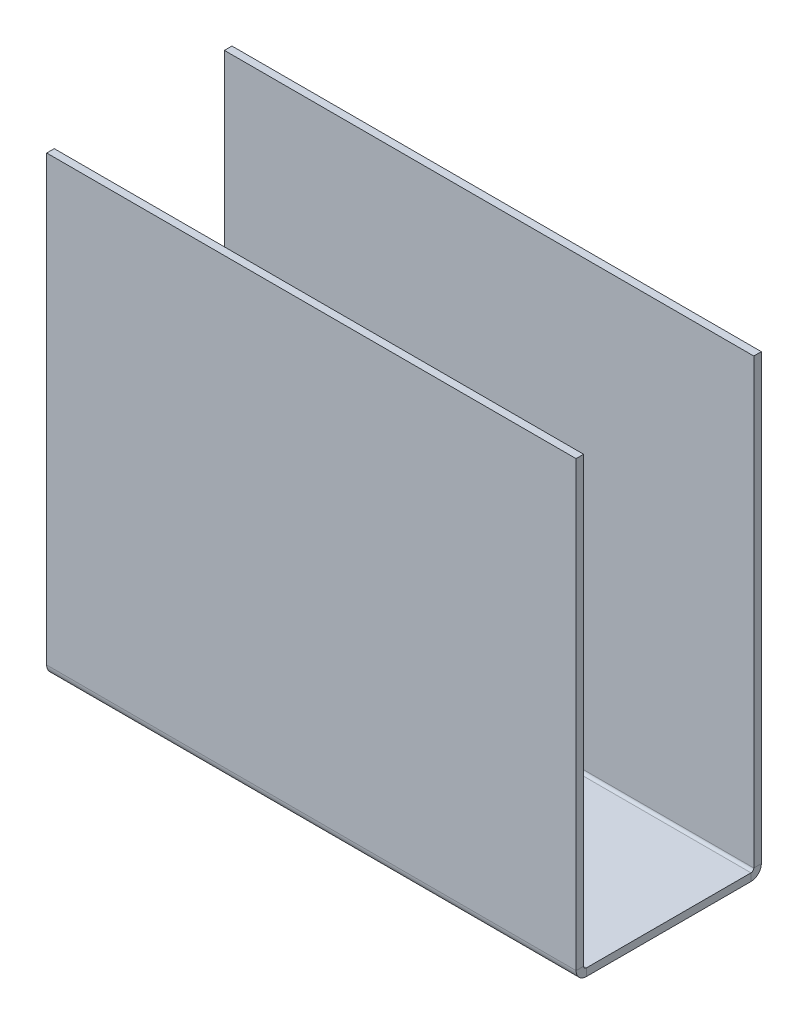
SolidWorks part; units mm, degrees
note: The reader was unsure of these and kept them because the rebuilt part matched: flange length of "Edge-Flange1".
ref_plane "Front Plane" through (0, 0, 0) normal (0, 0, 1) x (1, 0, 0)
ref_plane "Top Plane" through (0, 0, 0) normal (0, 1, 0) x (1, 0, 0)
ref_plane "Right Plane" through (0, 0, 0) normal (1, 0, 0) x (0, 0, -1)
sketch "Sketch1" plane through (0, 0, 0) normal (0, 1, 0) x (1, 0, 0)
  line L1 (-113.3849, 12.7788) -> (26.6151, 12.7788)
  line L2 (-113.3849, 12.7788) -> (-113.3849, -36.2212)
  line L3 (-113.3849, -36.2212) -> (26.6151, -36.2212)
  line L4 (26.6151, 12.7788) -> (26.6151, -36.2212)
  dimension "D1" = 140
  dimension "D2" = 49
base flange "Base-Flange1" sketch "Sketch1" thickness 2 reverse thickness direction no parameters "D1"=0.7366
edge flange "Edge-Flange1" sketch "Sketch8" flange profiles "Sketch8", "Sketch10" flange angle 90 flange length 120 flange position material inside bend radius 0.7366 thickness 2 relief rectangular parameters "D6"=10, "D8"=1
sketch "Sketch8" plane through (0, 0, -12.7788) normal (0, 0, -1) x (-1, 0, 0)
  line L0 (-26.6151, 0) -> (113.3849, 0) construction
  line L1 (-26.6151, 0) -> (113.3849, 0)
  line L2 (-26.6151, 0) -> (-26.6151, 118)
  line L3 (-26.6151, 118) -> (113.3849, 118)
  line L4 (113.3849, 118) -> (113.3849, 0)
sketch "Sketch10" plane through (0, 0, 36.2212) normal (0, 0, 1) x (1, 0, 0)
  line L0 (-113.3849, 0) -> (26.6151, 0) construction
  line L1 (-113.3849, 0) -> (26.6151, 0)
  line L2 (-113.3849, 0) -> (-113.3849, 118)
  line L3 (-113.3849, 118) -> (26.6151, 118)
  line L4 (26.6151, 118) -> (26.6151, 0)
bend "EdgeBend1" bend radius 0.7366 bend angle 90 parameters "D5"=1
bend "EdgeBend2" bend radius 0.7366 bend angle 90 parameters "D5"=3
sketch "Bend-Lines1" [suppressed] plane through (0, 0, 0) normal (0, 1, 0) x (1, 0, 0)
sketch "Bounding-Box1" [suppressed] plane through (0, 0, 0) normal (0, 1, 0) x (1, 0, 0)
sheet metal parameters "Sheet-Metal1" thickness 2 parameters "D1"=0.7366
flat pattern "Flat-Pattern1" [suppressed]
sketch "Bend-Lines2" plane through (0, 0, 0) normal (0, 1, 0) x (1, 0, 0)
sketch3d "Bounding-Box2" [suppressed]
  line L0 (-26.6151, -36.2212, 0) -> (313.3849, -36.2212, 0) construction
  line L1 (-26.6151, 12.7788, 0) -> (313.3849, 12.7788, 0) construction
  line L2 (-26.6151, -36.2212, 0) -> (-26.6151, 12.7788, 0) construction
  line L3 (313.3849, -36.2212, 0) -> (313.3849, 12.7788, 0) construction
sheet metal parameters "Sheet-Metal2" thickness 2 parameters "D1"=0.7366
flat pattern "Flat-Pattern1"
sketch "Bend-Lines2" plane through (0, 0, 0) normal (0, 1, 0) x (1, 0, 0)
  line L0 (26.6151, 11.4061) -> (-113.3849, 11.4061) construction
  line L1 (26.6151, 11.4061) -> (-113.3849, 11.4061) construction
  line L2 (-113.3849, -34.8485) -> (26.6151, -34.8485) construction
  line L3 (-113.3849, -34.8485) -> (26.6151, -34.8485) construction
sketch3d "Bounding-Box2" [suppressed]
  line L0 (-113.3849, 130.0334, 0) -> (-113.3849, -153.4759, 0) construction
  line L1 (26.6151, 130.0334, 0) -> (26.6151, -153.4759, 0) construction
  line L2 (-113.3849, 130.0334, 0) -> (26.6151, 130.0334, 0) construction
  line L3 (-113.3849, -153.4759, 0) -> (26.6151, -153.4759, 0) construction
bend of the flat pattern "Flatten-<EdgeBend1>1"
bend of the flat pattern "Flatten-<EdgeBend2>1"
